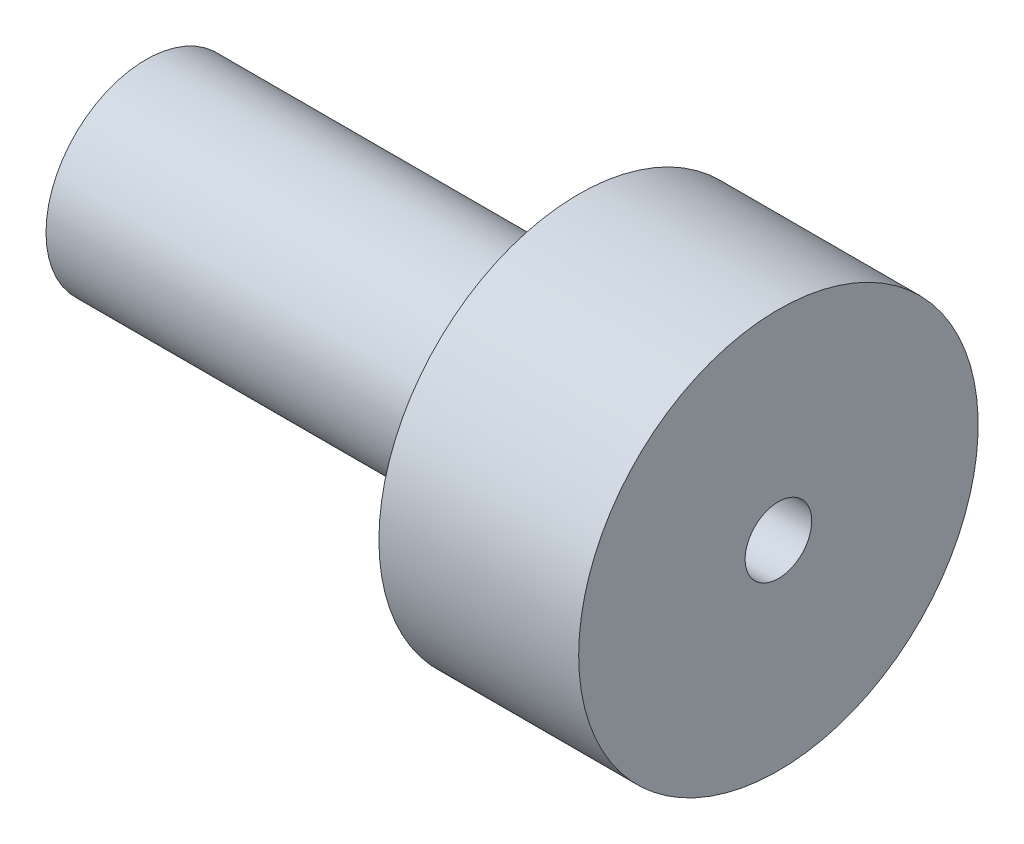
SolidWorks part; units mm, degrees
material "AISI 316 Stainless Steel Sheet (SS)"
ref_plane "Front Plane" through (0, 0, 0) normal (0, 0, 1) x (1, 0, 0)
ref_plane "Top Plane" through (0, 0, 0) normal (0, 1, 0) x (1, 0, 0)
ref_plane "Right Plane" through (0, 0, 0) normal (1, 0, 0) x (0, 0, -1)
sketch "Sketch1" plane through (0, 0, 0) normal (0, 0, 1) x (1, 0, 0)
  line L0 (0, 0) -> (0, 3)
  line L1 (0, 3) -> (13, 3)
  line L2 (13, 3) -> (13, 6)
  line L3 (13, 6) -> (19, 6)
  line L4 (19, 6) -> (19, 0)
  line L5 (19, 0) -> (0, 0)
  line L6 (0, 0) -> (-5.9552, 0) construction
  line L7 (-5.9552, 0) -> (25.4515, 0) construction
  dimension "D1" = 19
  dimension "D2" = 6
  dimension "D3" = 3
  dimension "D4" = 6
revolve "Revolve1" add sketch "Sketch1" angle 360 about L7
sketch "Sketch2" plane through (0, 0, 0) normal (1, 0, 0) x (0, 0, -1)
  circle A0 centre (0, 0) radius 1
  dimension "D1" = 2
extrude "Cut-Extrude2" cut sketch "Sketch2" along normal through all
